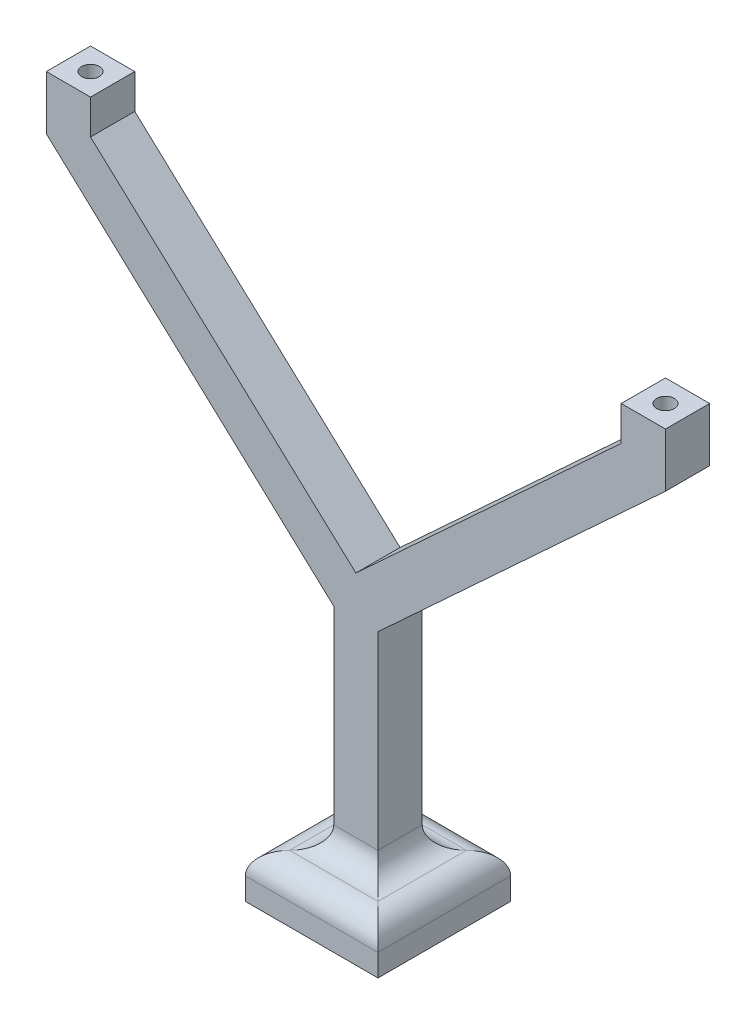
SolidWorks part; units mm, degrees
ref_plane "Front Plane" through (0, 0, 0) normal (0, 0, 1) x (1, 0, 0)
ref_plane "Top Plane" through (0, 0, 0) normal (0, 1, 0) x (1, 0, 0)
ref_plane "Right Plane" through (0, 0, 0) normal (1, 0, 0) x (0, 0, -1)
sketch "Sketch11" plane through (0, 0, 0) normal (0, 0, 1) x (1, 0, 0)
  line L0 (-65, 130) -> (-65, 120) construction
  line L1 (-65, 120) -> (0, 60) construction
  line L2 (-70, 130) -> (-70, 117.8108)
  line L3 (0, 0) -> (0, 60) construction
  line L4 (0, 60) -> (65, 120) construction
  line L5 (65, 120) -> (65, 130) construction
  line L6 (-70, 117.8108) -> (0, 53.1955)
  line L7 (0, 53.1955) -> (70, 117.8108)
  line L8 (70, 117.8108) -> (70, 130)
  line L9 (-60, 130) -> (-60, 122.1892)
  line L10 (-60, 122.1892) -> (0, 66.8045)
  line L11 (0, 66.8045) -> (60, 122.1892)
  line L12 (60, 122.1892) -> (60, 130)
  line L13 (-70, 130) -> (-60, 130)
  line L14 (60, 130) -> (70, 130)
  dimension "D1" = 130
  dimension "D2" = 130
  dimension "D3" = 10
  dimension "D4" = 60
  dimension "D5" = 5
  dimension "D6" = 5
extrude "Boss-Extrude3" add sketch "Sketch11" along normal mid plane 10
sketch "Sketch32" plane through (0, 0, 0) normal (0, 1, 0) x (1, 0, 0)
  line L0 (60, 5) -> (0, 5) construction
  line L1 (-5, -5) -> (5, -5)
  line L2 (-5, -5) -> (-5, 5)
  line L3 (-5, 5) -> (5, 5)
  line L4 (5, -5) -> (5, 5)
  line L5 (0, 5) -> (0, -5) construction
  line L6 (-5, 0) -> (5, 0) construction
  point P0 (0, 0)
extrude "Boss-Extrude5" add sketch "Sketch32" along normal up to vertex (66.8045 mm away) up to point (0, 66.8045, 5)
sketch "Sketch33" plane through (0, 0, 0) normal (0, -1, 0) x (1, 0, 0)
  line L1 (-15, -15) -> (15, -15)
  line L2 (-15, -15) -> (-15, 15)
  line L3 (-15, 15) -> (15, 15)
  line L4 (15, -15) -> (15, 15)
  line L5 (0, 15) -> (0, -15) construction
  line L6 (-15, 0) -> (15, 0) construction
  point P0 (0, 0)
  dimension "D1" = 30
extrude "Boss-Extrude6" add sketch "Sketch33" against normal blind 10
fillet "Fillet2" radius 5 8 edges at (0, 10, -5) (-5, 10, 0) (0, 10, 5) (5, 10, 0) (0, 10, 15) (-15, 10, 0) (0, 10, -15) (15, 10, 0)
sketch "Sketch34" plane through (0, 130, 0) normal (0, 1, 0) x (1, 0, 0)
  line L0 (-70, 5) -> (-60, -5) construction
  line L2 (60, -5) -> (70, 5) construction
  circle A0 centre (-65, 0) radius 2
  circle A1 centre (65, 0) radius 2
  dimension "D1" = 4
extrude "Cut-Extrude2" cut sketch "Sketch34" against normal blind 4
